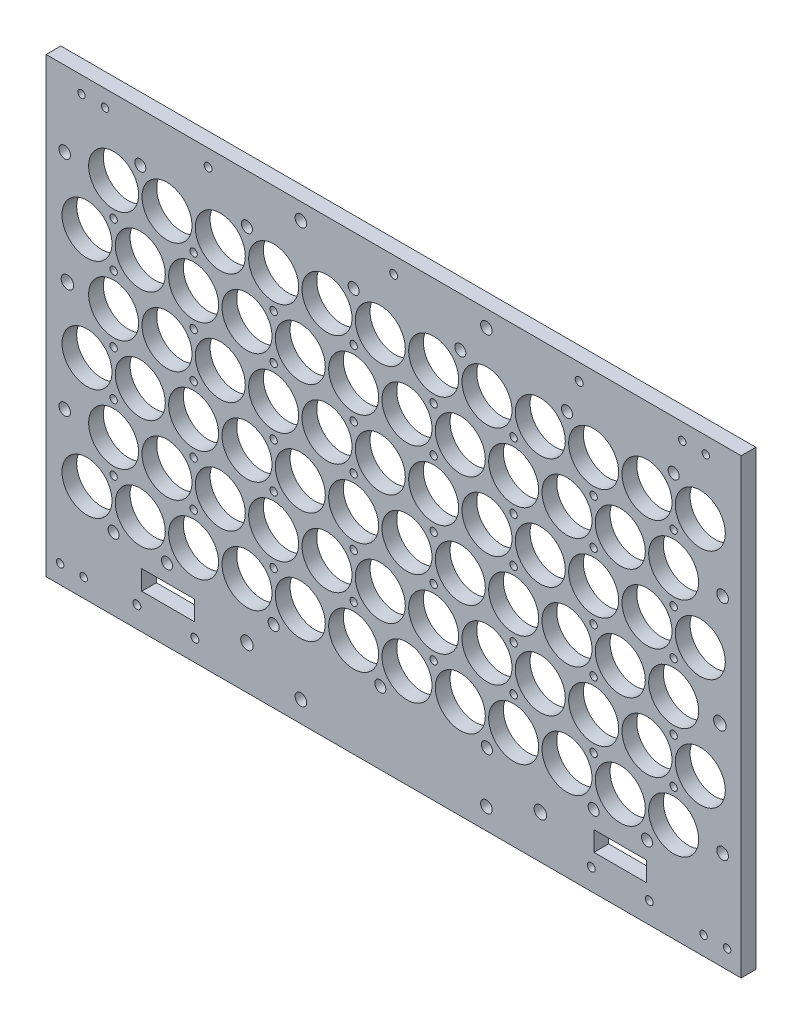
SolidWorks part; units mm, degrees
material "ABS"
ref_plane "X-Y Datum" through (0, 0, 0) normal (0, 0, 1) x (1, 0, 0)
ref_plane "X-Z Datum" through (0, 0, 0) normal (0, 1, 0) x (1, 0, 0)
ref_plane "Y-Z Datum" through (0, 0, 0) normal (1, 0, 0) x (0, 0, -1)
sketch "Sketch1" plane through (0, 0, 0) normal (0, 0, 1) x (1, 0, 0)
  line L1 (-143.025, 70.775) -> (143.025, 70.775)
  line L2 (-143.025, 70.775) -> (-143.025, -70.775)
  line L3 (-143.025, -70.775) -> (143.025, -70.775)
  line L4 (143.025, 70.775) -> (143.025, -70.775)
  line L5 (-143.025, 70.775) -> (143.025, -70.775) construction
  line L6 (-143.025, -70.775) -> (143.025, 70.775) construction
  line L13 (-149.85, -102.6) -> (149.85, -102.6)
  line L14 (-149.85, 91.65) -> (149.85, 91.65)
  line L15 (-149.85, 91.65) -> (-149.85, -102.6)
  line L16 (149.85, 91.65) -> (149.85, -102.6)
  line L17 (149.85, 70.775) -> (149.85, -70.775) construction
  line L18 (-143.025, 91.65) -> (143.025, 91.65) construction
  line L19 (-143.025, -102.6) -> (143.025, -102.6) construction
  line L20 (-149.85, 70.775) -> (-149.85, -70.775) construction
  line L21 (-132.25, -60) -> (-109.25, -60) construction
  circle A0 centre (-132.25, -60) radius 10.775
  circle A1 centre (-109.25, -60) radius 10.775 construction
  circle A2 centre (-120.75, -36) radius 10.775
  point P0 (0, 0)
  point P16 (-120.75, -60)
  dimension "D1" = 21.55
  dimension "D2" = 23
  dimension "D3" = 24
  dimension "D5" = 141.55
  dimension "D6" = 286.05
  dimension "D7" = 31.825
  dimension "D8" = 20.875
  dimension "D9" = 6.825
  dimension "D10" = 6.825
extrude "Boss-Extrude1" add sketch "Sketch1" along normal blind 6.35 contours A0 L3 L4 L1 L2 A2 | A2 | A0 | A0 L2 L3 | L1 L4 L3 L2 region at (2.4105, 0.9241, 0) region at (-140.6182, -68.3682, 0) region at (-132.25, -60, 0) region at (-146.2785, -5.475, 0) region at (-120.75, -36, 0)
sketch "Sketch3" plane through (0, 0, 6.35) normal (0, 0, 1) x (1, 0, 0)
  line L4 (143.025, 70.775) -> (-143.025, 70.775)
  line L5 (143.025, -70.775) -> (143.025, 70.775)
  line L6 (-143.025, -70.775) -> (143.025, -70.775)
  line L7 (-143.025, 70.775) -> (-143.025, -70.775)
  line L8 (143.025, 70.775) -> (-143.025, 70.775)
  line L9 (143.025, -70.775) -> (143.025, 70.775)
  line L10 (-143.025, -70.775) -> (143.025, -70.775)
  line L11 (-143.025, 70.775) -> (-143.025, -70.775)
  circle A1 centre (-120.75, -36) radius 10.775
  circle A2 centre (-120.75, -36) radius 10.775
  circle A3 centre (-132.25, -60) radius 10.775
  circle A4 centre (-132.25, -60) radius 10.775
  dimension "D1" = 0
  dimension "D2" = 0
  dimension "D3" = 0
extrude "Cut-Extrude1" cut sketch "Sketch3" against normal through all contours A4 region at (-132.25, -60, 6.35)
sketch "Sketch4" plane through (0, 0, 6.35) normal (0, 0, 1) x (1, 0, 0)
  line L4 (143.025, 70.775) -> (-143.025, 70.775)
  line L5 (143.025, -70.775) -> (143.025, 70.775)
  line L6 (-143.025, -70.775) -> (143.025, -70.775)
  line L7 (-143.025, 70.775) -> (-143.025, -70.775)
  line L8 (143.025, 70.775) -> (-143.025, 70.775)
  line L9 (143.025, -70.775) -> (143.025, 70.775)
  line L10 (-143.025, -70.775) -> (143.025, -70.775)
  line L11 (-143.025, 70.775) -> (-143.025, -70.775)
  circle A1 centre (-120.75, -36) radius 10.775
  circle A2 centre (-120.75, -36) radius 10.775
  circle A3 centre (-132.25, -60) radius 10.775
  circle A4 centre (-132.25, -60) radius 10.775
  dimension "D1" = 0
  dimension "D2" = 0
  dimension "D3" = 0
extrude "Cut-Extrude2" cut sketch "Sketch4" against normal through all contours A2 region at (-120.75, -36, 6.35)
pattern_linear "LPattern1" count 12 spacing 23 along (1, 0, 0) of "Cut-Extrude1", "Cut-Extrude2"
pattern_linear "LPattern2" count 3 spacing 48 along (0, 1, 0) of "LPattern1"
sketch "Sketch5" plane through (0, 0, 6.35) normal (0, 0, 1) x (1, 0, 0)
  line L4 (105.3154, -79.3475) -> (90.1846, -79.3475)
  line L5 (90.37, -80.3) -> (90.37, -83.4115)
  line L6 (90.37, -83.4115) -> (105.13, -83.4115)
  line L7 (105.13, -83.4115) -> (105.13, -80.3)
  line L8 (105.3154, -79.3475) -> (90.1846, -79.3475)
  line L9 (90.37, -80.3) -> (90.37, -83.4115)
  line L10 (90.37, -83.4115) -> (105.13, -83.4115)
  line L11 (105.13, -83.4115) -> (105.13, -80.3)
  line L12 (-108.668, -78.95) -> (-108.668, -87.4115)
  line L13 (-108.668, -87.4115) -> (-85.908, -87.4115)
  line L14 (-85.908, -87.4115) -> (-85.908, -78.95)
  line L15 (86.37, -78.95) -> (86.37, -87.4115)
  line L16 (-89.7226, -79.3475) -> (-104.8534, -79.3475)
  line L17 (-104.668, -80.3) -> (-104.668, -83.4115)
  line L18 (-104.668, -83.4115) -> (-89.908, -83.4115)
  line L19 (-89.908, -83.4115) -> (-89.908, -80.3)
  line L20 (-89.7226, -79.3475) -> (-104.8534, -79.3475)
  line L21 (-104.668, -80.3) -> (-104.668, -83.4115)
  line L22 (-104.668, -83.4115) -> (-89.908, -83.4115)
  line L23 (-89.908, -83.4115) -> (-89.908, -80.3)
  line L24 (86.37, -87.4115) -> (109.13, -87.4115)
  line L25 (109.13, -87.4115) -> (109.13, -78.95)
  line L26 (149.85, -78.95) -> (-149.85, -78.95) construction
  line L27 (149.85, -78.95) -> (-149.85, -78.95)
  line L28 (109.13, -87.4115) -> (109.13, -80.3) construction
  line L29 (86.37, -80.3) -> (86.37, -87.4115) construction
  line L30 (-85.908, -87.4115) -> (-85.908, -80.3) construction
  line L31 (-108.668, -80.3) -> (-108.668, -87.4115) construction
  arc A2 (90.37, -80.3) -> (90.1846, -79.3475) centre (87.83, -80.3) ccw
  arc A3 (105.3154, -79.3475) -> (105.13, -80.3) centre (107.67, -80.3) ccw
  arc A4 (90.37, -80.3) -> (90.1846, -79.3475) centre (87.83, -80.3) ccw
  arc A5 (105.3154, -79.3475) -> (105.13, -80.3) centre (107.67, -80.3) ccw
  arc A8 (-104.668, -80.3) -> (-104.8534, -79.3475) centre (-107.208, -80.3) ccw
  arc A9 (-89.7226, -79.3475) -> (-89.908, -80.3) centre (-87.368, -80.3) ccw
  arc A10 (-104.668, -80.3) -> (-104.8534, -79.3475) centre (-107.208, -80.3) ccw
  arc A11 (-89.7226, -79.3475) -> (-89.908, -80.3) centre (-87.368, -80.3) ccw
  dimension "D1" = 0
  dimension "D2" = 0
  dimension "D3" = 4
extrude "Cut-Extrude3" cut sketch "Sketch5" against normal through all contours L25 L27 L15 L24 L8 A5 L11 L10 L9 A4 | A5 L8 A4 L9 L10 L11 | L14 L27 L12 L13 L20 A11 L23 L22 L21 A10 | A11 L20 A10 L21 L22 L23 region at (97.75, -81.376, 6.35) region at (-97.288, -83.9995, 6.35) region at (97.75, -83.9995, 6.35) region at (-97.288, -81.376, 6.35)
sketch "Sketch7" plane through (0, 0, 6.35) normal (0, 0, 1) x (1, 0, 0)
  point P0 (0, 85.3)
  point P1 (80, 85.3)
  point P3 (-124.45, 85.3)
  point P5 (-134.61, 85.3)
  point P7 (-133.6575, -94.6)
  point P9 (-143.8175, -94.6)
  point P11 (133.6575, -94.6)
  point P13 (143.8175, -94.6)
  point P17 (124.45, 85.3)
  point P19 (134.61, 85.3)
  point P21 (110.25, -93.5057)
  point P23 (85.25, -93.5057)
  point P28 (-80, 85.3)
hole_wizard "M3 Clearance Hole1" positions "Sketch8" profile "Sketch9" hole size "M3" standard "ANSI Metric" end condition through all
sketch "Sketch8" plane through (0, 0, 6.35) normal (0, 0, 1) x (1, 0, 0)
  point P3 (124.45, 85.3)
  point P6 (134.61, 85.3)
  point P12 (-124.45, 85.3)
  point P15 (-134.61, 85.3)
  point P18 (-143.8175, -94.6)
  point P21 (-133.6575, -94.6)
  point P24 (133.6575, -94.6)
  point P27 (143.8175, -94.6)
sketch "Sketch9" plane through (124.45, 85.3, 6.35) normal (1, 0, 0) x (0, -1, 0)
  line L0 (0, 0) -> (0, 6.35)
  line L1 (0, 6.35) -> (1.6, 6.35)
  line L2 (1.6, 6.35) -> (1.6, 0)
  line L5 (1.6, 0) -> (0, 0)
  line L11 (0, -6.35) -> (0, 107.95) construction
  dimension "Thru Hole Dia." = 3.2
  dimension "Thru Hole Depth" = 6.35
hole_wizard "M3 Clearance Hole2" positions "Sketch20" profile "Sketch13" hole size "M3" standard "ANSI Metric" end condition through all
sketch "Sketch20" plane through (0, 0, 6.35) normal (0, 0, 1) x (1, 0, 0)
  point P0 (110.25, -93.5057)
  point P3 (85.25, -93.5057)
  point P6 (-80, 85.3)
  point P9 (0, 85.3)
  point P12 (80, 85.3)
sketch "Sketch13" plane through (110.25, -93.5057, 6.35) normal (1, 0, 0) x (0, -1, 0)
  line L0 (0, 0) -> (0, 6.35)
  line L1 (0, 6.35) -> (1.7, 6.35)
  line L2 (1.7, 6.35) -> (1.7, 0)
  line L5 (1.7, 0) -> (0, 0)
  line L11 (0, -6.35) -> (0, 107.95) construction
  dimension "Thru Hole Dia." = 3.4
  dimension "Thru Hole Depth" = 6.35
sketch "Sketch14" plane through (0, 0, 6.35) normal (0, 0, 1) x (1, 0, 0)
  line L0 (131.525, -12) -> (149.85, -12) construction
  line L1 (149.85, 91.65) -> (149.85, -102.6) construction
  line L2 (-131.525, 12) -> (-149.85, 12) construction
  line L3 (-149.85, 91.65) -> (-149.85, -102.6) construction
  line L4 (149.85, -78.95) -> (-149.85, -78.95) construction
  line L5 (149.85, -78.95) -> (-149.85, -78.95) construction
  line L6 (149.85, -83.95) -> (-149.85, -83.95) construction
  line L7 (68.55, -70.9014) -> (57.95, -70.9014) construction
  line L8 (68.55, -67.0427) -> (68.55, -74.76) construction
  line L9 (57.95, -67.0427) -> (57.95, -74.76) construction
  line L10 (63.25, -70.9014) -> (63.25, -83.95) construction
  line L18 (0, -3.4925) -> (0, 3.4925) construction
  circle A0 centre (120.75, -12) radius 10.775 construction
  circle A1 centre (-120.75, 12) radius 10.775 construction
  circle A2 centre (140.6875, -12) radius 2.7
  circle A3 centre (-140.6875, 12) radius 2.7
  circle A4 centre (63.25, -83.95) radius 2.7
  circle A6 centre (-63.25, -83.95) radius 2.7
  circle A8 centre (0, -83.95) radius 2.7
  dimension "D1" = 5.4
  dimension "D3" = 5.4
  dimension "D2" = 5
extrude "Cut-Extrude4" cut sketch "Sketch14" against normal through all contours A6 | A4 | A3 | A2 region at (-140.6875, 12, 6.35) region at (63.25, -83.95, 6.35) region at (-63.25, -83.95, 6.35)
sketch "Sketch15" plane through (0, 0, 6.35) normal (0, 0, 1) x (1, 0, 0)
  line L0 (-6.35, 85.3) -> (86.35, 85.3) construction
  line L1 (-6.35, 90.65) -> (-6.35, 79.95) construction
  line L2 (86.35, 79.95) -> (86.35, 90.65) construction
  line L3 (-86.35, 85.3) -> (6.35, 85.3) construction
  line L4 (-86.35, 90.65) -> (-86.35, 79.95) construction
  line L5 (6.35, 79.95) -> (6.35, 90.65) construction
  line L6 (131.525, 36) -> (149.85, 36) construction
  line L7 (149.85, 94.825) -> (149.85, -105.775) construction
  line L8 (131.525, -60) -> (149.85, -60) construction
  line L9 (-131.525, -36) -> (-149.85, -36) construction
  line L10 (-149.85, -105.775) -> (-149.85, 94.825) construction
  line L11 (-131.525, 60) -> (-149.85, 60) construction
  line L12 (-40, 85.3) -> (-40, -102.6) construction
  line L13 (-149.85, -102.6) -> (149.85, -102.6) construction
  line L14 (40, 85.3) -> (40, -102.6) construction
  line L16 (85.25, -93.5057) -> (-85.25, -93.5057) construction
  circle A0 centre (-40, 85.3) radius 2.5
  circle A1 centre (40, 85.3) radius 2.5
  circle A2 centre (120.75, 36) radius 10.775 construction
  circle A3 centre (120.75, -60) radius 10.775 construction
  circle A4 centre (141.85, 36) radius 2.5
  circle A5 centre (141.85, -60) radius 2.5
  circle A6 centre (-120.75, -36) radius 10.775 construction
  circle A7 centre (-120.75, 60) radius 10.775 construction
  circle A8 centre (-141.85, -36) radius 2.5
  circle A9 centre (-141.85, 60) radius 2.5
  circle A10 centre (-40, -93.5057) radius 2.5
  circle A11 centre (40, -93.5057) radius 2.5
  dimension "D1" = 5
  dimension "D2" = 8
  dimension "D3" = 8
  dimension "D4" = 8
  dimension "D5" = 8
extrude "Cut-Extrude5" cut sketch "Sketch15" against normal through all
sketch "Sketch18" plane through (0, 0, 6.35) normal (0, 0, 1) x (1, 0, 0)
  circle A0 centre (-120.75, -71.41) radius 1.5875 construction
  circle A1 centre (-97.75, -71.41) radius 1.5875 construction
  circle A2 centre (-51.75, -71.41) radius 1.5875 construction
  circle A3 centre (-5.75, -71.41) radius 1.5875 construction
  circle A4 centre (40.25, -71.41) radius 1.5875 construction
  circle A5 centre (-109.25, 71.41) radius 1.5875 construction
  circle A6 centre (-63.25, 71.41) radius 1.5875 construction
  circle A7 centre (-17.25, 71.41) radius 1.5875 construction
  circle A8 centre (28.75, 71.41) radius 1.5875 construction
  circle A9 centre (74.75, 71.41) radius 1.5875 construction
  circle A10 centre (120.75, 71.41) radius 1.5875 construction
  circle A11 centre (86.25, -71.41) radius 1.5875 construction
  circle A12 centre (109.25, -71.41) radius 1.5875 construction
  circle A13 centre (-120.75, -71.41) radius 1.5875 construction
  circle A14 centre (-97.75, -71.41) radius 1.5875 construction
  circle A15 centre (-51.75, -71.41) radius 1.5875 construction
  circle A16 centre (-5.75, -71.41) radius 1.5875 construction
  circle A17 centre (40.25, -71.41) radius 1.5875 construction
  circle A18 centre (-109.25, 71.41) radius 1.5875 construction
  circle A19 centre (-63.25, 71.41) radius 1.5875 construction
  circle A20 centre (-17.25, 71.41) radius 1.5875 construction
  circle A21 centre (28.75, 71.41) radius 1.5875 construction
  circle A22 centre (74.75, 71.41) radius 1.5875 construction
  circle A23 centre (120.75, 71.41) radius 1.5875 construction
  circle A24 centre (86.25, -71.41) radius 1.5875 construction
  circle A25 centre (109.25, -71.41) radius 1.5875 construction
  circle A26 centre (109.25, -71.41) radius 2.3813
  circle A27 centre (86.25, -71.41) radius 2.3813
  circle A28 centre (120.75, 71.41) radius 2.3813
  circle A29 centre (74.75, 71.41) radius 2.3813
  circle A30 centre (28.75, 71.41) radius 2.3813
  circle A31 centre (-17.25, 71.41) radius 2.3812
  circle A32 centre (-63.25, 71.41) radius 2.3812
  circle A33 centre (-109.25, 71.41) radius 2.3813
  circle A34 centre (40.25, -71.41) radius 2.3812
  circle A35 centre (-5.75, -71.41) radius 2.3812
  circle A36 centre (-51.75, -71.41) radius 2.3812
  circle A37 centre (-97.75, -71.41) radius 2.3813
  circle A38 centre (-120.75, -71.41) radius 2.3813
  dimension "D1" = 4.7625
extrude "Cut-Extrude7" cut sketch "Sketch18" against normal through all
sketch "Sketch19" plane through (0, 91.65, 0) normal (0, 1, 0) x (1, 0, 0)
  line L4 (149.85, 0) -> (-149.85, 0)
  line L5 (-149.85, 0) -> (-149.85, -6.35)
  line L6 (-149.85, -6.35) -> (149.85, -6.35)
  line L7 (149.85, -6.35) -> (149.85, 0)
  line L8 (149.85, 0) -> (-149.85, 0)
  line L9 (-149.85, 0) -> (-149.85, -6.35)
  line L10 (-149.85, -6.35) -> (149.85, -6.35)
  line L11 (149.85, -6.35) -> (149.85, 0)
  dimension "D1" = 0
extrude "Boss-Extrude2" add sketch "Sketch19" along normal blind 0.7937
sketch "Sketch22" plane through (0, 0, 6.35) normal (0, 0, 1) x (1, 0, 0)
  line L0 (132.25, -36) -> (120.75, -60) construction
  line L1 (120.75, -60) -> (109.25, -36) construction
  line L2 (109.25, -36) -> (132.25, -36) construction
  line L3 (120.75, -36) -> (120.75, -60) construction
  line L4 (127.5939, -45.7171) -> (113.9061, -45.7171) construction
  line L5 (109.25, -36) -> (97.75, -60) construction
  line L6 (97.75, -60) -> (86.25, -36) construction
  line L7 (86.25, -36) -> (109.25, -36) construction
  line L8 (97.75, -60) -> (97.75, -36) construction
  line L9 (113.9061, -45.7171) -> (90.9061, -45.7171) construction
  line L10 (86.25, -36) -> (74.75, -60) construction
  line L11 (74.75, -60) -> (63.25, -36) construction
  line L12 (63.25, -36) -> (86.25, -36) construction
  line L13 (74.75, -36) -> (74.75, -60) construction
  line L14 (90.9061, -45.7171) -> (67.9061, -45.7171) construction
  line L15 (74.75, -60) -> (97.75, -60) construction
  line L16 (86.25, -36) -> (86.25, -60) construction
  line L17 (79.4061, -50.2829) -> (93.0939, -50.2829) construction
  circle A0 centre (132.25, -36) radius 10.775 construction
  circle A1 centre (109.25, -36) radius 10.775 construction
  circle A2 centre (120.75, -45.7171) radius 1.5875
  circle A3 centre (86.25, -36) radius 10.775 construction
  circle A6 centre (74.75, -60) radius 10.775 construction
  circle A7 centre (97.75, -60) radius 10.775 construction
  circle A8 centre (86.25, -50.2829) radius 1.5875
  dimension "D1" = 3.175
extrude "Cut-Extrude8" cut sketch "Sketch22" against normal through all
pattern_linear "LPattern3" count 3 spacing 48 along (0, 1, 0) of "Cut-Extrude8"
sketch "Sketch23" plane through (0, 0, 6.35) normal (0, 0, 1) x (1, 0, 0)
  line L0 (132.25, -36) -> (120.75, -12) construction
  line L1 (120.75, -12) -> (109.25, -36) construction
  line L2 (109.25, -36) -> (132.25, -36) construction
  line L3 (120.75, -36) -> (120.75, -12) construction
  line L4 (109.25, -36) -> (97.75, -12) construction
  line L5 (97.75, -12) -> (86.25, -36) construction
  line L6 (86.25, -36) -> (109.25, -36) construction
  line L7 (97.75, -36) -> (97.75, -12) construction
  line L8 (127.5939, -26.2829) -> (90.9061, -26.2829) construction
  line L9 (86.25, -36) -> (63.25, -36) construction
  line L10 (63.25, -36) -> (74.75, -12) construction
  line L11 (74.75, -12) -> (86.25, -36) construction
  line L12 (74.75, -36) -> (74.75, -12) construction
  line L13 (90.9061, -26.2829) -> (67.9061, -26.2829) construction
  line L14 (74.75, -12) -> (97.75, -12)
  line L15 (86.25, -12) -> (86.25, -36) construction
  line L16 (79.4061, -21.7171) -> (93.0939, -21.7171) construction
  circle A0 centre (132.25, -36) radius 10.775 construction
  circle A1 centre (86.25, -36) radius 10.775 construction
  circle A2 centre (120.75, -26.2829) radius 1.5875
  circle A5 centre (74.75, -12) radius 10.775 construction
  circle A6 centre (97.75, -12) radius 10.775 construction
  circle A7 centre (86.25, -21.7171) radius 1.5875
  dimension "D1" = 3.175
extrude "Cut-Extrude9" cut sketch "Sketch23" against normal through all contours A7 | A2 region at (120.75, -26.2829, 6.35) region at (86.25, -21.7171, 6.35)
pattern_linear "LPattern4" count 2 spacing 48 along (0, 1, 0) of "Cut-Extrude9"
pattern_linear "LPattern5" count 4 spacing 69 along (-1, 0, 0) of "Cut-Extrude8", "LPattern3", "Cut-Extrude9", "LPattern4"
sketch "Sketch25" plane through (0, 0, 6.35) normal (0, 0, 1) x (1, 0, 0)
  line L0 (-85.712, -93.486) -> (-110.712, -93.486)
  line L1 (-149.85, -102.6) -> (149.85, -102.6) construction
  line L3 (-149.85, 92.4437) -> (-149.85, -102.6) construction
  circle A0 centre (-110.712, -93.486) radius 1.5
  circle A1 centre (-85.712, -93.486) radius 1.5
  point P2 (-97.9237, -93.5058)
  point P7 (-98.212, -93.486)
  dimension "D1" = 3
  dimension "D2" = 25
  dimension "D3" = 9.114
  dimension "D4" = 39.138
hole_wizard "M3 Clearance Hole3" positions "Sketch30" profile "Sketch29" hole size "M3" standard "ANSI Metric" end condition through all
sketch "Sketch30" plane through (0, 0, 6.35) normal (0, 0, 1) x (1, 0, 0)
  point P0 (-85.712, -93.486)
  point P3 (-110.712, -93.486)
sketch "Sketch29" plane through (-85.712, -93.486, 6.35) normal (1, 0, 0) x (0, -1, 0)
  line L0 (0, 0) -> (0, 6.35)
  line L1 (0, 6.35) -> (1.7, 6.35)
  line L2 (1.7, 6.35) -> (1.7, 0)
  line L5 (1.7, 0) -> (0, 0)
  line L11 (0, -6.35) -> (0, 107.95) construction
  dimension "Thru Hole Dia." = 3.4
  dimension "Thru Hole Depth" = 6.35
